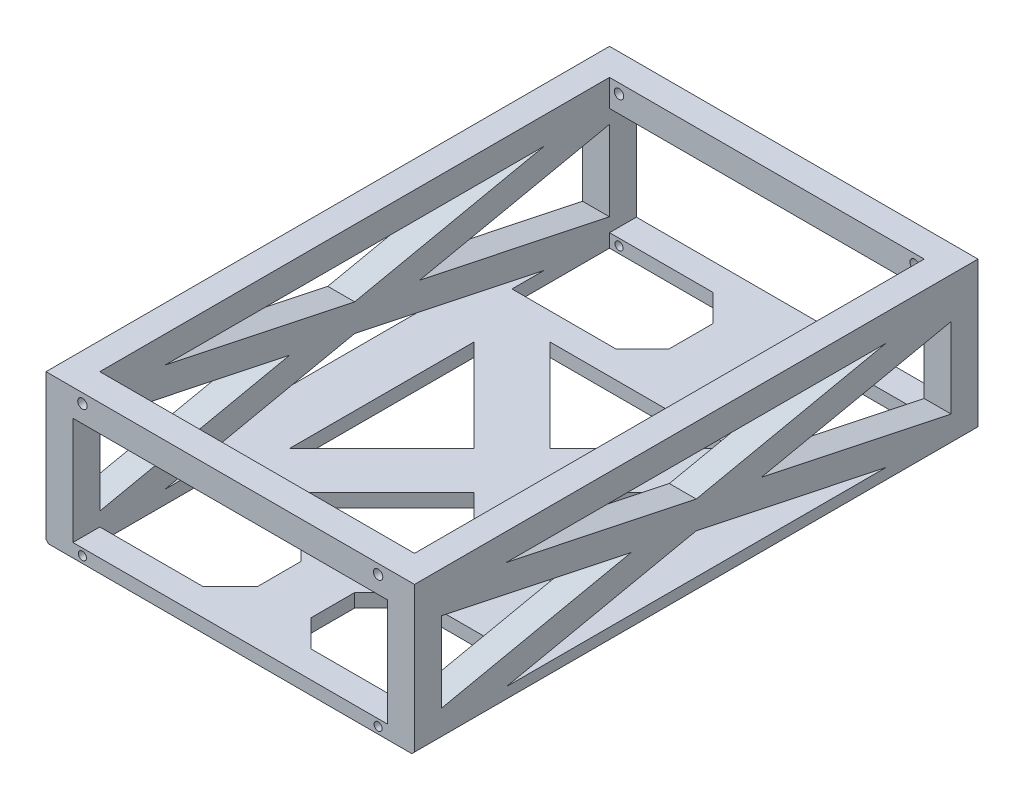
SolidWorks part; units mm, degrees
ref_plane "Front Plane" through (0, 0, 0) normal (0, 0, 1) x (1, 0, 0)
ref_plane "Top Plane" through (0, 0, 0) normal (0, 1, 0) x (1, 0, 0)
ref_plane "Right Plane" through (0, 0, 0) normal (1, 0, 0) x (0, 0, -1)
sketch "Sketch1" plane through (0, 0, 0) normal (0, 1, 0) x (1, 0, 0)
  line L1 (-68.5, -104.75) -> (68.5, -104.75)
  line L2 (-68.5, -104.75) -> (-68.5, 104.75)
  line L3 (-68.5, 104.75) -> (68.5, 104.75)
  line L4 (68.5, -104.75) -> (68.5, 104.75)
  line L5 (-68.5, -104.75) -> (68.5, 104.75) construction
  line L6 (-68.5, 104.75) -> (68.5, -104.75) construction
  line L7 (-58.5, -94.75) -> (58.5, -94.75)
  line L8 (-58.5, -94.75) -> (-58.5, 94.75)
  line L9 (-58.5, 94.75) -> (58.5, 94.75)
  line L10 (58.5, -94.75) -> (58.5, 94.75)
  line L11 (-58.5, -94.75) -> (58.5, 94.75) construction
  line L12 (-58.5, 94.75) -> (58.5, -94.75) construction
  point P0 (0, 0)
  point P6 (0, 0)
  dimension "D1" = 137
  dimension "D2" = 209.5
  dimension "D3" = 10
  dimension "D4" = 10
extrude "Boss-Extrude1" add sketch "Sketch1" along normal blind 5
sketch "Sketch2" plane through (0, 5, 0) normal (0, 1, 0) x (1, 0, 0)
  line L1 (-68.5, 104.75) -> (-58.5, 104.75)
  line L2 (-68.5, 104.75) -> (-68.5, 94.75)
  line L3 (-68.5, 94.75) -> (-58.5, 94.75)
  line L4 (-58.5, 104.75) -> (-58.5, 94.75)
  line L5 (68.5, 104.75) -> (58.5, 104.75)
  line L6 (68.5, 104.75) -> (68.5, 94.75)
  line L7 (68.5, 94.75) -> (58.5, 94.75)
  line L8 (58.5, 104.75) -> (58.5, 94.75)
  line L9 (-68.5, -104.75) -> (-58.5, -104.75)
  line L10 (-68.5, -104.75) -> (-68.5, -94.75)
  line L11 (-68.5, -94.75) -> (-58.5, -94.75)
  line L12 (-58.5, -104.75) -> (-58.5, -94.75)
  line L13 (68.5, -104.75) -> (58.5, -104.75)
  line L14 (68.5, -104.75) -> (68.5, -94.75)
  line L15 (68.5, -94.75) -> (58.5, -94.75)
  line L16 (58.5, -104.75) -> (58.5, -94.75)
extrude "Boss-Extrude2" add sketch "Sketch2" along normal blind 50
sketch "Sketch3" plane through (58.5, 0, 0) normal (-1, 0, 0) x (0, 0, 1)
  line L0 (-94.75, 55) -> (-94.75, 5) construction
  line L1 (-104.75, 55) -> (-94.75, 55)
  line L2 (-104.75, 55) -> (-104.75, 45)
  line L3 (-104.75, 45) -> (-94.75, 45)
  line L4 (-94.75, 55) -> (-94.75, 45)
  line L5 (104.75, 55) -> (104.75, 5) construction
  line L6 (94.75, 55) -> (104.75, 55)
  line L7 (94.75, 55) -> (94.75, 45)
  line L8 (94.75, 45) -> (104.75, 45)
  line L9 (104.75, 55) -> (104.75, 45)
extrude "Boss-Extrude3" add sketch "Sketch3" along normal up to surface (117 mm away) up to face at (-58.5, 30, -99.75)
sketch "Sketch4" plane through (0, 0, -94.75) normal (0, 0, 1) x (1, 0, 0)
  line L1 (-58.5, 45) -> (-68.5, 45)
  line L2 (-58.5, 45) -> (-58.5, 55)
  line L3 (-58.5, 55) -> (-68.5, 55)
  line L4 (-68.5, 45) -> (-68.5, 55)
  line L5 (58.5, 45) -> (68.5, 45)
  line L6 (58.5, 45) -> (58.5, 55)
  line L7 (58.5, 55) -> (68.5, 55)
  line L8 (68.5, 45) -> (68.5, 55)
extrude "Boss-Extrude4" add sketch "Sketch4" along normal up to surface (189.5 mm away) up to face at (0, 27.5, 94.75)
sketch "Sketch5" plane through (0, 0, 0) normal (0, -1, 0) x (1, 0, 0)
  line L0 (-58.5, -58.5) -> (58.5, -58.5)
  line L1 (-58.5, -94.75) -> (-58.5, 94.75) construction
  line L2 (58.5, 94.75) -> (58.5, -94.75) construction
  line L3 (-58.5, 58.5) -> (58.5, 58.5)
  line L4 (58.5, -94.75) -> (-58.5, -94.75) construction
  line L5 (-58.5, 94.75) -> (58.5, 94.75) construction
  line L6 (-58.5, -58.5) -> (58.5, 58.5)
  line L7 (58.5, -58.5) -> (-58.5, 58.5)
  line L8 (-48.5, -34.3579) -> (-14.1421, 0)
  line L9 (-14.1421, 0) -> (-48.5, 34.3579)
  line L10 (-48.5, 34.3579) -> (-48.5, -34.3579)
  line L11 (-58.5, -58.5) -> (-58.5, 58.5)
  line L12 (58.5, 58.5) -> (58.5, -58.5)
  line L13 (34.3579, 48.5) -> (-34.3579, 48.5)
  line L14 (-34.3579, 48.5) -> (0, 14.1421)
  line L15 (0, 14.1421) -> (34.3579, 48.5)
  line L16 (48.5, -34.3579) -> (48.5, 34.3579)
  line L17 (48.5, 34.3579) -> (14.1421, 0)
  line L18 (14.1421, 0) -> (48.5, -34.3579)
  line L19 (-34.3579, -48.5) -> (34.3579, -48.5)
  line L20 (34.3579, -48.5) -> (0, -14.1421)
  line L21 (0, -14.1421) -> (-34.3579, -48.5)
  line L22 (0, 76.625) -> (0, 0)
  line L23 (-10, 94.75) -> (10, 94.75)
  line L24 (-10, 94.75) -> (-10, 58.5)
  line L25 (-10, 58.5) -> (10, 58.5)
  line L26 (10, 94.75) -> (10, 58.5)
  line L27 (-10, 94.75) -> (10, 58.5) construction
  line L28 (-10, 58.5) -> (10, 94.75) construction
  line L29 (-10, -58.5) -> (10, -58.5)
  line L30 (-10, -58.5) -> (-10, -94.75)
  line L31 (-10, -94.75) -> (10, -94.75)
  line L32 (10, -58.5) -> (10, -94.75)
  line L33 (-10, -58.5) -> (10, -94.75) construction
  line L34 (-10, -94.75) -> (10, -58.5) construction
  line L35 (0, 0) -> (0, -76.625)
  circle A0 centre (0, 0) radius 14.1421
  point P17 (0, 76.625)
  point P30 (0, 0)
  point P33 (0, -76.625)
  line M20 (-58.5, 94.75) -> (58.5, 94.75)
  line M21 (58.5, 94.75) -> (58.5, -94.75)
  line M22 (58.5, -94.75) -> (-58.5, -94.75)
  line M23 (-58.5, -94.75) -> (-58.5, 94.75)
  dimension "D1" = 4
  dimension "D2" = 20
  dimension "D3" = 10
  dimension "D4" = 10
  dimension "D5" = 10
extrude "Boss-Extrude5" add sketch "Sketch5" against normal up to surface (5 mm away) contours L26 L24 L3 M20 | L32 L29 L0 L30 M22 | A0 L20 L19 L35 L29 L0 L7 | A0 L6 L0 L35 L19 L21 | A0 L7 L6 L17 L16 L18 M21 | A0 L6 L3 L22 L13 L15 | A0 L14 L13 L22 L3 L7 | A0 L7 L6 L8 L10 L9 M23 | L7 A0 L6 | L22 A0 L7 | L6 A0 L22 | L7 A0 L6 | L35 A0 L7 | L6 A0 L35 region at (-33.7127, 0, -34.7873) region at (-57.2335, 0, 0) region at (-5, 0, -58.914) region at (-8.4883, 0, 0) region at (-3.516, 0, -8.4883) region at (-34.25, 0, 57.7401) region at (0.7599, 0, -53.5) region at (3.516, 0, 8.4883) region at (8.4883, 0, 0) region at (-3.516, 0, 8.4883) region at (3.516, 0, -8.4883) region at (-9.586, 0, 76.625) region at (5.7028, 0, 13.7677) region at (35.1456, 0, 33.3544) up to face at (63.5, 5, 0)
chamfer "Chamfer1" distance 10 angle 45 8 edges at (10, 2.5, 58.5) (-10, 2.5, 58.5) (-10, 2.5, 94.75) (10, 2.5, 94.75) (-10, 2.5, -94.75) (-10, 2.5, -58.5) (10, 2.5, -94.75) (10, 2.5, -58.5)
sketch "Sketch7" plane through (-68.5, 0, 0) normal (-1, 0, 0) x (0, 0, 1)
  line L0 (-94.75, 45) -> (94.75, 5)
  line L1 (94.75, 45) -> (-94.75, 5)
  line L2 (-94.75, 45) -> (-70.5405, 45)
  line L3 (94.75, 45) -> (-94.75, 45) construction
  line L4 (-70.5405, 45) -> (94.75, 10.1102)
  line L5 (94.75, 45) -> (94.75, 5) construction
  line L6 (94.75, 10.1102) -> (94.75, 5)
  line L7 (-94.75, 45) -> (-94.75, 39.8898)
  line L8 (-94.75, 45) -> (-94.75, 5) construction
  line L9 (-94.75, 39.8898) -> (70.5405, 5)
  line L10 (-94.75, 5) -> (94.75, 5) construction
  line L11 (70.5405, 5) -> (94.75, 5)
  line L12 (94.75, 45) -> (70.5405, 45)
  line L13 (70.5405, 45) -> (-94.75, 10.1102)
  line L14 (-94.75, 10.1102) -> (-94.75, 5)
  line L15 (94.75, 45) -> (94.75, 39.8898)
  line L16 (94.75, 39.8898) -> (-70.5405, 5)
  line L17 (-70.5405, 5) -> (-94.75, 5)
  line M11 (-94.75, 5) -> (-94.75, 45)
  line M12 (-94.75, 45) -> (94.75, 45)
  line M13 (94.75, 45) -> (94.75, 5)
  line M14 (94.75, 5) -> (-94.75, 5)
  dimension "D1" = 5
  dimension "D2" = 5
  dimension "D3" = 5
  dimension "D4" = 5
extrude "Boss-Extrude6" add sketch "Sketch7" against normal up to surface (10 mm away) contours L13 L4 L0 M12 | L13 L0 L9 M11 | L13 L4 L1 M12 | L4 L16 L0 M13 | L0 L16 L9 M14 | L16 L9 L1 M14 | L9 L13 L1 M11 | L4 L13 L0 L1 | L0 L13 L9 L1 | L16 L0 L1 L9 | L16 L4 L1 L0 | L16 L1 L4 M13 region at (-68.5, 36.8995, -44.5879) region at (-68.5, 34.4117, -56.3738) region at (-68.5, 27.5551, 0) region at (-68.5, 25, -12.1047) region at (-68.5, 25, 12.1047) region at (-68.5, 22.4449, 0) region at (-68.5, 36.8995, 44.5879) region at (-68.5, 15.5883, -56.3738) region at (-68.5, 15.5883, 56.3738) region at (-68.5, 13.1005, 44.5879) region at (-68.5, 34.4117, 56.3738) region at (-68.5, 13.1005, -44.5879) up to face at (-58.5, 50, 0)
extrude "Boss-Extrude7" add sketch "Sketch7<3>" along normal up to surface (-127 mm away) from surface contours L13 L4 L0 M12 | L13 L0 L9 M11 | L13 L4 L1 M12 | L16 L1 L4 M13 | L4 L16 L0 M13 | L0 L16 L9 M14 | L16 L9 L1 M14 | L9 L13 L1 M11 | L0 L13 L9 L1 | L4 L13 L0 L1 | L16 L4 L1 L0 | L16 L0 L1 L9 region at (-68.5, 36.8995, -44.5879) region at (-68.5, 34.4117, -56.3738) region at (-68.5, 27.5551, 0) region at (-68.5, 25, -12.1047) region at (-68.5, 25, 12.1047) region at (-68.5, 22.4449, 0) region at (-68.5, 36.8995, 44.5879) region at (-68.5, 15.5883, -56.3738) region at (-68.5, 15.5883, 56.3738) region at (-68.5, 13.1005, 44.5879) region at (-68.5, 34.4117, 56.3738) region at (-68.5, 13.1005, -44.5879) up to face at (58.5, 50, 0) starting at face at (68.5, 25, 0)
sketch "Sketch7<3>" plane through (-68.5, 0, 0) normal (-1, 0, 0) x (0, 0, 1) same geometry as "Sketch7"
sketch "Sketch8" plane through (0, 0, 104.75) normal (0, 0, 1) x (1, 0, 0)
  line L0 (-68.5, 55) -> (68.5, 55) construction
  line L1 (-58.5, 55) -> (58.5, 55)
  line L2 (-58.5, 55) -> (-58.5, 0)
  line L3 (-58.5, 0) -> (58.5, 0)
  line L4 (58.5, 55) -> (58.5, 0)
  line L5 (-68.5, 0) -> (68.5, 0) construction
  line L6 (58.5, 45) -> (58.5, 5) construction
  line L7 (-58.5, 45) -> (-58.5, 5) construction
  line L8 (-58.5, 5) -> (58.5, 5) construction
  line L9 (-58.5, 0) -> (-51.42, 0)
  line L10 (-58.5, 0) -> (-58.5, 5)
  line L11 (-58.5, 5) -> (-51.42, 5)
  line L12 (-51.42, 0) -> (-51.42, 5)
  line L13 (-58.5, 55) -> (-51.42, 47.92)
  line L14 (58.5, 0) -> (51.42, 0)
  line L15 (58.5, 0) -> (58.5, 5)
  line L16 (58.5, 5) -> (51.42, 5)
  line L17 (51.42, 0) -> (51.42, 5)
  line L18 (-58.5, 55) -> (-51.42, 55)
  line L19 (-58.5, 55) -> (-58.5, 47.92)
  line L20 (-58.5, 47.92) -> (-51.42, 47.92)
  line L21 (-51.42, 55) -> (-51.42, 47.92)
  line L22 (58.5, 55) -> (51.42, 55)
  line L23 (58.5, 55) -> (58.5, 47.92)
  line L24 (58.5, 47.92) -> (51.42, 47.92)
  line L25 (51.42, 55) -> (51.42, 47.92)
  line L26 (58.5, 55) -> (51.42, 47.92)
  line L27 (51.42, 5) -> (58.5, 0)
  line L28 (-58.5, 5) -> (-51.42, 0)
  circle A0 centre (-54.96, 51.46) radius 1.75
  circle A1 centre (54.96, 51.46) radius 1.75
  circle A2 centre (-54.96, 2.5) radius 1.5
  circle A3 centre (54.96, 2.5) radius 1.5
  dimension "D2" = 3.5
  dimension "D3" = 3
  dimension "D1" = 7.08
extrude "Cut-Extrude1" cut sketch "Sketch8" against normal up to surface (209.5 mm away) contours L13 A0 | L13 A0 | L26 A1 | L26 A1 | L27 A3 | L27 A3 | L28 A2 | L28 A2 region at (-54.4348, 51.9852, 104.75) region at (-55.4852, 50.9348, 104.75) region at (-54.5928, 3.02, 104.75) region at (-55.3272, 1.98, 104.75) region at (55.4852, 50.9348, 104.75) region at (54.4348, 51.9852, 104.75) region at (54.5928, 1.98, 104.75) region at (55.3272, 3.02, 104.75) up to face at (0, 25, -104.75)
chamfer "Chamfer2" distance 1 angle 45 2 edges at (68.5, 0, 0) (-68.5, 0, 0)
equation "\"side spoke\"=5"
equation "\"D1@Sketch7\"=\"side spoke\""
equation "\"D2@Sketch7\"=\"side spoke\""
equation "\"D3@Sketch7\"=\"side spoke\""
equation "\"D4@Sketch7\"=\"side spoke\""
